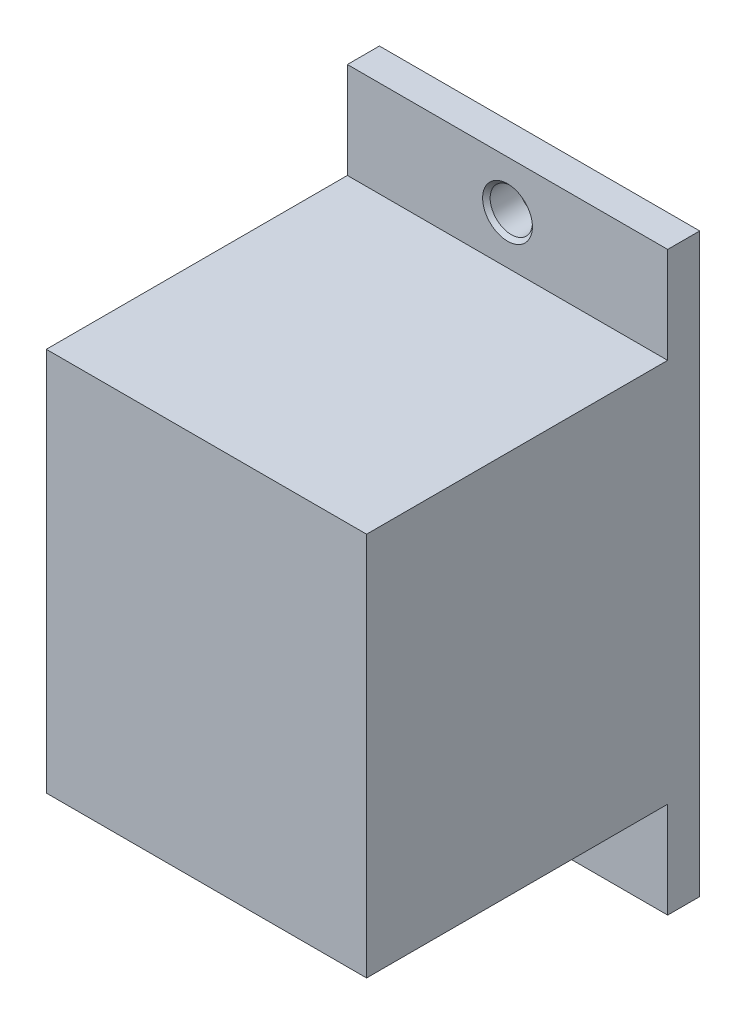
SolidWorks part; units mm, degrees
ref_plane "Plano frontal" through (0, 0, 0) normal (1, 0, 0) x (0, 1, 0)
ref_plane "Plano superior" through (0, 0, 0) normal (0, 0, 1) x (0, 1, 0)
ref_plane "Plano direito" through (0, 0, 0) normal (0, 1, 0) x (-1, 0, 0)
sketch "Esboço1" plane through (0, 0, 0) normal (0, 0, 1) x (0, 1, 0)
  line L0 (-28, -23) -> (-28, 23)
  line L1 (-30, -25) -> (30, -25)
  line L2 (-30, -25) -> (-30, 25)
  line L3 (-30, 25) -> (30, 25)
  line L4 (30, -25) -> (30, 25)
  line L5 (-30, -25) -> (30, 25) construction
  line L6 (-30, 25) -> (30, -25) construction
  line L7 (30, 25) -> (45, 25)
  line L8 (30, 25) -> (30, -25)
  line L9 (30, -25) -> (45, -25)
  line L10 (45, 25) -> (45, -25)
  line L11 (-30, 25) -> (-45, 25)
  line L12 (-30, 25) -> (-30, -25)
  line L13 (-30, -25) -> (-45, -25)
  line L14 (-45, 25) -> (-45, -25)
  line L15 (-28, 23) -> (28, 23)
  line L16 (28, -23) -> (28, 23)
  line L17 (-28, -23) -> (28, -23)
  point P0 (0, 0)
  point P10 (0, 0)
  point P11 (0, 0)
  point P12 (0, 0)
  point P13 (0, 0)
  point P14 (0, 0)
  point P15 (0, 0)
  point P16 (-27.5, -19)
  point P21 (0, 0)
  dimension "D1" = 50
  dimension "D2" = 60
  dimension "D3" = 15
  dimension "D4" = 15
  dimension "D5" = 2
extrude "Ressalto-extrusão1" add sketch "Esboço1" along normal blind 5 contours L12 L11 L14 L13 | L8 L7 L10 L9
extrude "Ressalto-extrusão2" add sketch "Esboço1<4>" along normal blind 50 contours L1 L4 L3 L2 L17 L0 L15 L16 region at (0, -29.219, 0)
sketch "Esboço1<4>" plane through (0, 0, 0) normal (0, 0, 1) x (0, 1, 0) same geometry as "Esboço1"
sketch "Esboço3" plane through (0, 0, 50) normal (0, 0, 1) x (1, 0, 0)
  line L1 (-25, 30) -> (25, 30)
  line L2 (-25, 30) -> (-25, -30)
  line L3 (-25, -30) -> (25, -30)
  line L4 (25, 30) -> (25, -30)
extrude "Ressalto-extrusão3" add sketch "Esboço3" along normal blind 2
sketch "Esboço4" plane through (0, 0, 5) normal (0, 0, 1) x (0, -1, 0)
  circle A1 centre (-37.5, 0) radius 3.5
  circle A2 centre (37.5, 0) radius 3.5
  point P0 (37.5, 0)
  point P2 (-37.5, 0)
  dimension "D1" = 7
  dimension "D2" = 7
hole_wizard "Furo roscado de G1/164" positions "Esboço4" profile "Esboço6" tap size "G1/16" standard "ISO" end condition through all
sketch "Esboço6" plane through (0, -37.5, 5) normal (1, 0, 0) x (0, -1, 0)
  line L0 (0, 0) -> (0, 5)
  line L1 (0, 5) -> (3.3, 5)
  line L2 (3.3, 5) -> (3.3, 0.5865)
  line L3 (3.3, 0.5865) -> (3.8865, 0)
  line L5 (3.8865, 0) -> (0, 0)
  line L6 (-3.3, 0.5865) -> (-3.8865, 0) construction
  line L11 (0, -6.35) -> (0, 107.95) construction
  dimension "Thru Tap Drill Dia." = 6.6
  dimension "Thru Tap Drill Depth" = 5
  dimension "Near C'Sink Dia." = 7.773
  dimension "Near C'Sink Angle" = 90
cosmetic thread "Rosca de furo1" parameters "D2"=7.723
cosmetic thread "Rosca de furo2" parameters "D2"=7.723
